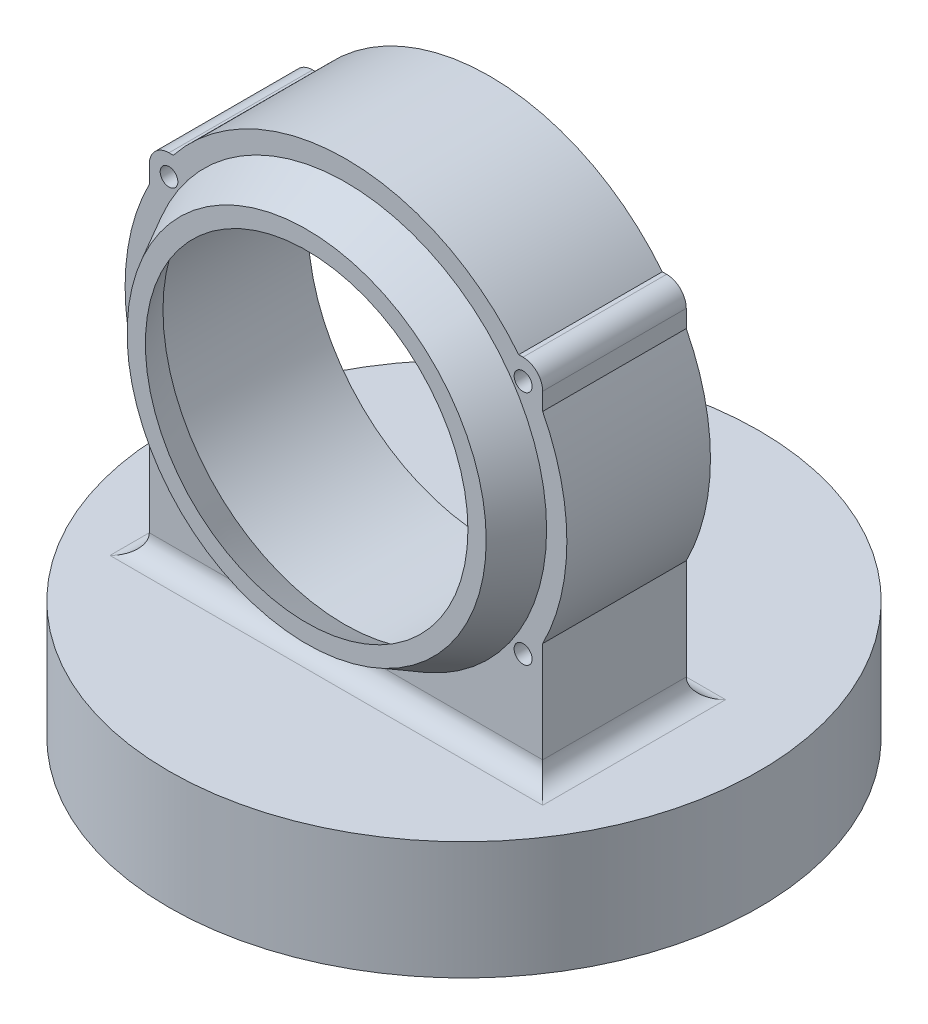
SolidWorks part; units mm, degrees
ref_plane "Alzado" through (0, 0, 0) normal (0, 0, 1) x (1, 0, 0)
ref_plane "Planta" through (0, 0, 0) normal (0, 1, 0) x (1, 0, 0)
ref_plane "Vista lateral" through (0, 0, 0) normal (1, 0, 0) x (0, 0, -1)
sketch "Croquis1" plane through (0, 0, 0) normal (0, 1, 0) x (1, 0, 0)
  circle A0 centre (0, 0) radius 75
  dimension "D1" = 150
extrude "Saliente-Extruir1" add sketch "Croquis1" along normal blind 30
sketch "Croquis2" plane through (0, 30, 0) normal (0, 1, 0) x (1, 0, 0)
  circle A0 centre (0, 0) radius 14.285
  dimension "D1" = 28.57
extrude "Cortar-Extruir1" cut sketch "Croquis2" along normal blind 10 from surface starting at face at (0, 0, 75)
sketch "Croquis3" plane through (0, 0, 0) normal (0, 0, 1) x (1, 0, 0)
  line L0 (43.907, 121.15) -> (45, 121.15)
  line L1 (50, 60.5996) -> (50, 30)
  line L2 (0, 0) -> (0, 85.4991) construction
  line L10 (-45, 121.15) -> (-43.907, 121.15)
  line L11 (-50, 116.15) -> (-50, 111.7004)
  line L12 (-50, 30) -> (50, 30)
  line L13 (50, 116.15) -> (50, 111.7004)
  line L14 (75, 30) -> (-75, 30) construction
  line L15 (-50, 60.5996) -> (-50, 30)
  circle A0 centre (0, 86.15) radius 46.15
  circle A1 centre (0, 86.15) radius 56.15
  arc A2 (45, 121.15) -> (50, 116.15) centre (45, 116.15) cw
  arc A3 (-45, 121.15) -> (-50, 116.15) centre (-45, 116.15) ccw
  point P5 (-0.8152, 30)
  point P17 (50, 121.15)
  point P20 (-50, 121.15)
  dimension "D4" = 92.3
  dimension "D6" = 5
  dimension "D1" = 100
  dimension "D2" = 10
  dimension "D3" = 35
  dimension "D5" = 50
extrude "Saliente-Extruir2" add sketch "Croquis3" against normal blind 36.5 from offset 30 contours A1 L15 L12 | A1 L12 L1 | L10 A3 L11 A1 | A2 L0 A1 L13 | A1 | A0 region at (47.8302, 117.6386, 0) region at (-47.8302, 117.6386, 0) region at (38.2791, 38.5026, 0) region at (-38.2791, 38.5026, 0)
sketch "Croquis5" plane through (0, 0, 30) normal (0, 0, 1) x (1, 0, 0)
  circle A0 centre (0, 86.15) radius 41
  circle A1 centre (0, 86.15) radius 51
  circle A2 centre (0, 86.15) radius 46.15 construction
  circle A3 centre (0, 86.15) radius 46.15 construction
  dimension "D1" = 82
  dimension "D2" = 10
extrude "Saliente-Extruir3" add sketch "Croquis5" along normal blind 10
chamfer "Chaflán1" distance 10 angle 28.15 1 edges at (41, 86.15, 30) first distance on face at (41, 86.15, 40)
chamfer "Chaflán2" distance 10 angle 28.15 1 edges at (51, 86.15, 40) first distance on face at (51, 86.15, 40)
fillet "Redondeo1" radius 5 4 edges at (0, 30, -6.5) (-50, 30, 11.75) (0, 30, 30) (50, 30, 11.75)
sketch "Croquis7" plane through (0, 0, -6.5) normal (0, 0, -1) x (-1, 0, 0)
  line L0 (0, 85.85) -> (71.2114, 85.85) construction
  circle A0 centre (44.9882, 115.8636) radius 2.2483
  circle A1 centre (-45.0262, 115.8636) radius 2.2831
  circle A2 centre (-45.0262, 55.8364) radius 2.2831
  circle A3 centre (44.9882, 55.8364) radius 2.2483
  dimension "D3" = 4.4965
  dimension "D1" = 30.0136
  dimension "D2" = 44.9882
extrude "Cortar-Extruir2" cut sketch "Croquis7" against normal through all
